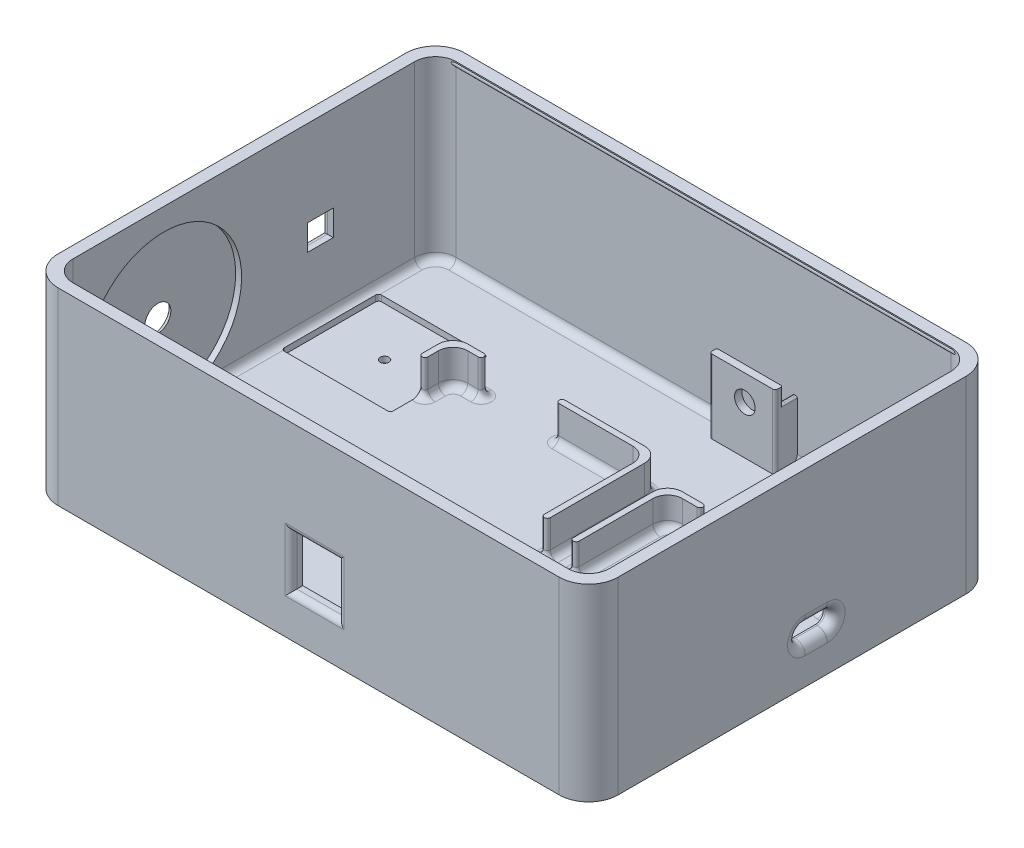
SolidWorks part; units mm, degrees
ref_plane "Front Plane" through (0, 0, 0) normal (0, 0, 1) x (1, 0, 0)
ref_plane "Top Plane" through (0, 0, 0) normal (0, 1, 0) x (1, 0, 0)
ref_plane "Right Plane" through (0, 0, 0) normal (1, 0, 0) x (0, 0, -1)
sketch "Sketch1" plane through (0, 0, 0) normal (0, 1, 0) x (1, 0, 0)
  line L0 (-95, -69) -> (-95, 69)
  line L1 (-91, -65) -> (91, -65)
  line L2 (-91, -65) -> (-91, 65)
  line L3 (-91, 65) -> (91, 65)
  line L4 (91, -65) -> (91, 65)
  line L5 (-91, -65) -> (91, 65) construction
  line L6 (-91, 65) -> (91, -65) construction
  line L7 (-95, 69) -> (95, 69)
  line L8 (95, -69) -> (95, 69)
  line L9 (-95, -69) -> (95, -69)
  point P0 (0, 0)
  dimension "D2" = 130
  dimension "D3" = 182
  dimension "D1" = 4
extrude "Box Sides" add sketch "Sketch1" along normal blind 60
fillet "Fillet1" radius 7 4 edges at (91, 30, 65) (91, 30, -65) (-91, 30, 65) (-91, 30, -65)
fillet "Fillet2" radius 10 4 edges at (95, 30, -69) (95, 30, 69) (-95, 30, 69) (-95, 30, -69)
sketch "Sketch2" plane through (0, 0, 0) normal (0, -1, 0) x (1, 0, 0)
  line L0 (-95, 59) -> (-95, -59)
  line L1 (-85, -69) -> (85, -69)
  line L2 (95, -59) -> (95, 59)
  line L3 (85, 69) -> (-85, 69)
  line L4 (-85, -69) -> (85, -69)
  line L5 (95, -59) -> (95, 59)
  line L6 (85, 69) -> (-85, 69)
  line L7 (-95, 59) -> (-95, -59)
  line L8 (-85, -69) -> (85, -69)
  line L9 (95, -59) -> (95, 59)
  line L10 (85, 69) -> (-85, 69)
  line L11 (-95, 59) -> (-95, -59)
  arc A0 (-85, 69) -> (-95, 59) centre (-85, 59) ccw
  arc A1 (-95, -59) -> (-85, -69) centre (-85, -59) ccw
  arc A2 (85, -69) -> (95, -59) centre (85, -59) ccw
  arc A3 (95, 59) -> (85, 69) centre (85, 59) ccw
  arc A4 (85, -69) -> (95, -59) centre (85, -59) ccw
  arc A5 (95, 59) -> (85, 69) centre (85, 59) ccw
  arc A6 (-85, 69) -> (-95, 59) centre (-85, 59) ccw
  arc A7 (-95, -59) -> (-85, -69) centre (-85, -59) ccw
  arc A8 (85, -69) -> (95, -59) centre (85, -59) ccw
  arc A9 (95, 59) -> (85, 69) centre (85, 59) ccw
  arc A10 (-85, 69) -> (-95, 59) centre (-85, 59) ccw
  arc A11 (-95, -59) -> (-85, -69) centre (-85, -59) ccw
  line M9 (-85, -69) -> (85, -69)
  arc M10 (85, -69) -> (95, -59) centre (85, -59) ccw
  line M11 (95, -59) -> (95, 59)
  arc M12 (95, 59) -> (85, 69) centre (85, 59) ccw
  line M13 (85, 69) -> (-85, 69)
  arc M14 (-85, 69) -> (-95, 59) centre (-85, 59) ccw
  line M15 (-95, 59) -> (-95, -59)
  arc M16 (-95, -59) -> (-85, -69) centre (-85, -59) ccw
  line M17 (-84, 65) -> (84, 65)
  arc M18 (84, 65) -> (91, 58) centre (84, 58) cw
  line M19 (91, 58) -> (91, -58)
  arc M20 (91, -58) -> (84, -65) centre (84, -58) cw
  line M21 (84, -65) -> (-84, -65)
  arc M22 (-84, -65) -> (-91, -58) centre (-84, -58) cw
  line M23 (-91, -58) -> (-91, 58)
  arc M24 (-91, 58) -> (-84, 65) centre (-84, 58) cw
  dimension "D1" = 0
extrude "Bottom" add sketch "Sketch2" along normal blind 4 contours M17 M24 M23 M22 M21 M20 M19 M18 | M16 M9 M10 M11 M12 M13 M14 M15 M24 M17 M18 M19 M20 M21 M22 M23 region at (-90.4106, 0, 64.4106) region at (0, 0, 0)
sketch "Sketch3" plane through (-95, 0, 0) normal (-1, 0, 0) x (0, 0, 1)
  line L1 (-30.35, 22.1) -> (-21.65, 22.1)
  line L2 (-30.35, 22.1) -> (-30.35, 30.8)
  line L3 (-30.35, 30.8) -> (-21.65, 30.8)
  line L4 (-59, 60) -> (-59, -4)
  line L5 (-59, -4) -> (59, -4)
  line L6 (59, -4) -> (59, 60)
  line L7 (59, 60) -> (-59, 60)
  line L8 (-59, 60) -> (-59, -4)
  line L9 (-59, -4) -> (59, -4)
  line L10 (59, -4) -> (59, 60)
  line L11 (59, 60) -> (-59, 60)
  line L12 (-21.65, 22.1) -> (-21.65, 30.8)
  line L13 (-30.35, 22.1) -> (-21.65, 30.8) construction
  line L14 (-30.35, 30.8) -> (-21.65, 22.1) construction
  line L19 (-58, 0) -> (58, 0) construction
  circle A8 centre (27.15, 26.1) radius 4.35
  point P2 (-26, 26.45)
  point P9 (27.15, 26.1)
  point P16 (0, 60)
  dimension "D4" = 8.7
  dimension "D2" = 26
  dimension "D3" = 27.15
  dimension "D5" = 8.7
  dimension "D6" = 26.1
  dimension "D7" = 26.1
  dimension "D1" = 0
extrude "Camera Holes" cut sketch "Sketch3" against normal up to next contours L2 L1 L12 L3 | A8
sketch "Sketch4" plane through (0, 0, 0) normal (0, 1, 0) x (1, 0, 0)
  line L0 (27.8, 25) -> (37.8, 25)
  line L1 (27.8, 25) -> (27.8, -5)
  line L3 (81, 27) -> (91, 27)
  line L4 (-84, -65) -> (84, -65)
  line L5 (91, -58) -> (91, 58)
  line L6 (84, 65) -> (-84, 65)
  line L7 (-91, 58) -> (-91, -58)
  line L8 (-84, -65) -> (84, -65)
  line L9 (91, -58) -> (91, 58)
  line L10 (84, 65) -> (-84, 65)
  line L11 (-91, 58) -> (-91, -58)
  line L12 (27.8, -35) -> (27.8, -65)
  line L13 (25.8, 27) -> (37.8, 27)
  line L14 (25.8, 27) -> (25.8, -5)
  line L15 (81, 25) -> (91, 25)
  line L16 (25.8, -35) -> (25.8, -65)
  line L17 (25.8, -65) -> (27.8, -65)
  line L18 (91, 27) -> (91, 25)
  arc A0 (37.8, 25) -> (37.8, 27) centre (37.8, 26) ccw
  arc A1 (27.8, -5) -> (25.8, -5) centre (26.8, -5) cw
  arc A2 (81, 27) -> (81, 25) centre (81, 26) ccw
  arc A4 (-91, -58) -> (-84, -65) centre (-84, -58) ccw
  arc A5 (84, -65) -> (91, -58) centre (84, -58) ccw
  arc A6 (91, 58) -> (84, 65) centre (84, 58) ccw
  arc A7 (-84, 65) -> (-91, 58) centre (-84, 58) ccw
  arc A8 (-91, -58) -> (-84, -65) centre (-84, -58) ccw
  arc A9 (84, -65) -> (91, -58) centre (84, -58) ccw
  arc A10 (91, 58) -> (84, 65) centre (84, 58) ccw
  arc A11 (-84, 65) -> (-91, 58) centre (-84, 58) ccw
  arc A12 (27.8, -35) -> (25.8, -35) centre (26.8, -35) ccw
  dimension "D8" = 2
  dimension "D2" = 63.2
  dimension "D3" = 10
  dimension "D4" = 10
  dimension "D5" = 90
  dimension "D6" = 30
  dimension "D7" = 30
  dimension "D1" = 0
extrude "Battery Cage" add sketch "Sketch4" along normal blind 10 contours A1 L1 L0 A0 L13 L14 | L3 A2 L15 L9 | L12 A12 L16 L8 | L3 L18 L15 A2 region at (27.4453, 0, -10) region at (85.605, 0, -26) region at (26.8, 0, 49.6065)
sketch "Sketch5" plane through (0, 0, 0) normal (0, 1, 0) x (1, 0, 0)
  line L0 (16, -65) -> (16, -35)
  line L1 (16, 30) -> (16, -5)
  line L2 (-54.4, -30) -> (-54.4, -65)
  line L3 (16, 30) -> (-14, 30)
  line L4 (-41.5, 30) -> (-50, 30)
  line L5 (-50, 30) -> (-50, 21.5)
  line L7 (-60.5, 21.5) -> (-60.5, 38.9191)
  line L8 (-60.5, 38.9191) -> (-41.5, 38.9191)
  line L10 (91, -58) -> (91, 25)
  line L11 (91, 25) -> (81, 25)
  line L12 (81, 27) -> (91, 27)
  line L13 (91, 27) -> (91, 58)
  line L14 (84, 65) -> (-84, 65)
  line L15 (-91, 58) -> (-91, -58)
  line L16 (-84, -65) -> (25.8, -65)
  line L17 (25.8, -65) -> (25.8, -35)
  line L18 (27.8, -35) -> (27.8, -65)
  line L19 (27.8, -65) -> (84, -65)
  line L20 (91, -58) -> (91, 25)
  line L21 (91, 25) -> (81, 25)
  line L22 (81, 27) -> (91, 27)
  line L23 (91, 27) -> (91, 58)
  line L24 (84, 65) -> (-84, 65)
  line L25 (-91, 58) -> (-91, -58)
  line L26 (-84, -65) -> (25.8, -65)
  line L27 (25.8, -65) -> (25.8, -35)
  line L28 (27.8, -35) -> (27.8, -65)
  line L29 (27.8, -65) -> (84, -65)
  line L30 (-41.5, 32) -> (-52, 32)
  line L31 (-52, 32) -> (-52, 21.5)
  line L32 (18, 32) -> (18, -5)
  line L33 (18, 32) -> (-14, 32)
  line L34 (18, -65) -> (18, -35)
  line L35 (-50, -65) -> (-50, -30)
  line L36 (-54.4, -65) -> (-50, -65)
  line L37 (16, -65) -> (18, -65)
  arc A0 (-41.5, 30) -> (-41.5, 32) centre (-41.5, 31) ccw
  arc A1 (-50, 21.5) -> (-52, 21.5) centre (-51, 21.5) cw
  arc A2 (16, -5) -> (18, -5) centre (17, -5) ccw
  arc A3 (-14, 30) -> (-14, 32) centre (-14, 31) cw
  arc A5 (16, -35) -> (18, -35) centre (17, -35) cw
  arc A8 (-50, -30) -> (-54.4, -30) centre (-52.2, -30) ccw
  arc A9 (81, 27) -> (81, 25) centre (81, 26) ccw
  arc A10 (91, 58) -> (84, 65) centre (84, 58) ccw
  arc A11 (-84, 65) -> (-91, 58) centre (-84, 58) ccw
  arc A12 (-91, -58) -> (-84, -65) centre (-84, -58) ccw
  arc A13 (27.8, -35) -> (25.8, -35) centre (26.8, -35) ccw
  arc A14 (-60.5, 21.5) -> (-50, 21.5) centre (-55.25, 21.5) ccw
  arc A15 (84, -65) -> (91, -58) centre (84, -58) ccw
  arc A17 (81, 27) -> (81, 25) centre (81, 26) ccw
  arc A18 (91, 58) -> (84, 65) centre (84, 58) ccw
  arc A19 (-84, 65) -> (-91, 58) centre (-84, 58) ccw
  arc A20 (-91, -58) -> (-84, -65) centre (-84, -58) ccw
  arc A21 (27.8, -35) -> (25.8, -35) centre (26.8, -35) ccw
  arc A23 (84, -65) -> (91, -58) centre (84, -58) ccw
  dimension "D2" = 66
  dimension "D3" = 95
  dimension "D4" = 8.5
  dimension "D5" = 8.5
  dimension "D6" = 30
  dimension "D7" = 35
  dimension "D8" = 2
  dimension "D9" = 73
  dimension "D10" = 4.4
  dimension "D11" = 10.5
  dimension "D1" = 0
extrude "Pi Cage" add sketch "Sketch5" along normal blind 12 contours L1 A2 L32 L33 A3 L3 | A1 L31 L30 A0 L4 L5 | L35 A8 L2 L36 | L0 A5 L34 L37
fillet "Fillet3" radius 5 10 edges at (27.8, 5, -25) (91, 5, -25) (27.8, 5, 65) (25.8, 5, -27) (16, 6, 65) (-50, 6, 65) (18, 6, -32) (-50, 6, -30) (-52, 6, -32) (16, 6, -30)
fillet "Fillet4" radius 2.5 1 edges at (-95, 26.1, 31.5)
sketch "Sketch14" plane through (95, 0, 0) normal (1, 0, 0) x (0, 0, -1)
  line L0 (4.5, 11.2) -> (12, 11.2) construction
  line L1 (4.5, 13.8) -> (12, 13.8)
  line L2 (4.5, 8.6) -> (12, 8.6)
  line L3 (25.5, 60) -> (25.5, -4) construction
  line L4 (-59, 60) -> (-59, -4)
  line L5 (-59, -4) -> (59, -4)
  line L6 (59, -4) -> (59, 60)
  line L7 (59, 60) -> (-59, 60)
  line L8 (-59, 60) -> (-59, -4)
  line L9 (-59, -4) -> (59, -4)
  line L10 (59, -4) -> (59, 60)
  line L11 (59, 60) -> (-59, 60)
  line L12 (-65, 60) -> (-65, 0) construction
  arc A0 (4.5, 13.8) -> (4.5, 8.6) centre (4.5, 11.2) ccw
  arc A1 (12, 8.6) -> (12, 13.8) centre (12, 11.2) ccw
  point P6 (8.25, 11.2)
  dimension "D2" = 90.5
  dimension "D4" = 2.6
  dimension "D3" = 5.2
  dimension "D5" = 7.5
  dimension "D7" = 15.2
  dimension "D8" = 17.25
  dimension "D1" = 0
extrude "Power Button" cut sketch "Sketch14" against normal up to next contours L2 A1 L1 A0 region at (95, 11.2, -8.25)
fillet "Fillet5" radius 3.4 4 edges at (95, 11.2, -1.9) (95, 13.8, -8.25) (95, 11.2, -14.6) (95, 8.6, -8.25)
sketch "Sketch15" plane through (0, 0, 69) normal (0, 0, 1) x (1, 0, 0)
  line L0 (16, 0) -> (16, 12) construction
  line L1 (-6, 27.5) -> (10, 27.5)
  line L2 (-6, 27.5) -> (-6, 10)
  line L3 (-6, 10) -> (10, 10)
  line L4 (-85, 60) -> (-85, -4)
  line L5 (-85, -4) -> (85, -4)
  line L6 (85, -4) -> (85, 60)
  line L7 (85, 60) -> (-85, 60)
  line L8 (-85, 60) -> (-85, -4)
  line L9 (-85, -4) -> (85, -4)
  line L10 (85, -4) -> (85, 60)
  line L11 (85, 60) -> (-85, 60)
  line L12 (10, 27.5) -> (10, 10)
  line L13 (-6, 27.5) -> (10, 10) construction
  line L14 (-6, 10) -> (10, 27.5) construction
  point P2 (2, 18.75)
  dimension "D2" = 16
  dimension "D3" = 17.5
  dimension "D4" = 6
  dimension "D5" = 14
  dimension "D1" = 0
extrude "USBs" cut sketch "Sketch15" against normal up to next contours L2 L1 L12 L3
fillet "Fillet6" radius 2 4 edges at (2, 27.5, 69) (10, 18.75, 69) (-6, 18.75, 69) (2, 10, 69)
sketch "Sketch17" plane through (0, 0, 0) normal (0, 1, 0) x (1, 0, 0)
  line L0 (11, 60) -> (30.3, 60)
  line L1 (85, 69) -> (-85, 69) construction
  line L2 (11, 57.5) -> (30.3, 57.5)
  line L3 (20.65, 57.5) -> (20.65, 27.5) construction
  line L4 (11, 60) -> (11, 65)
  line L6 (30.3, 60) -> (30.3, 65)
  line L7 (84, 65) -> (-84, 65) construction
  line L8 (11, 65) -> (9.5, 65)
  line L9 (9.5, 65) -> (9.5, 58.4)
  line L10 (10.4, 57.5) -> (11, 57.5)
  line L11 (30.3, 57.5) -> (30.9, 57.5)
  line L12 (31.8, 58.4) -> (31.8, 65)
  line L13 (31.8, 65) -> (30.3, 65)
  line L16 (-45, -65) -> (11, -65)
  line L20 (-45, -65) -> (11, -65)
  line L24 (16, -60) -> (16, -35)
  line L28 (16, -60) -> (16, -35)
  line L66 (18, -35) -> (18, -65)
  line L68 (18, -35) -> (18, -65)
  line L84 (18, -65) -> (25.8, -65)
  line L92 (18, -65) -> (25.8, -65)
  line L100 (25.8, -65) -> (25.8, -35)
  line L104 (25.8, -65) -> (25.8, -35)
  line L108 (27.8, -35) -> (27.8, -60)
  line L111 (27.8, -35) -> (27.8, -60)
  line L113 (32.8, -65) -> (84, -65)
  line L115 (32.8, -65) -> (84, -65)
  line L117 (91, -58) -> (91, 20)
  line L119 (91, -58) -> (91, 20)
  line L121 (86, 25) -> (81, 25)
  line L122 (86, 25) -> (81, 25)
  line L123 (81, 27) -> (91, 27)
  line L124 (81, 27) -> (91, 27)
  line L125 (91, 27) -> (91, 58)
  line L126 (91, 27) -> (91, 58)
  line L127 (84, 65) -> (-84, 65)
  line L128 (84, 65) -> (-84, 65)
  line L129 (-91, 58) -> (-91, -58)
  line L130 (-91, 58) -> (-91, -58)
  line L131 (-84, -65) -> (-54.4, -65)
  line L132 (-84, -65) -> (-54.4, -65)
  line L133 (-50, -30) -> (-50, -60)
  line L134 (-50, -30) -> (-50, -60)
  line L135 (-54.4, -65) -> (-54.4, -30)
  line L136 (-54.4, -65) -> (-54.4, -30)
  arc A2 (9.5, 58.4) -> (10.4, 57.5) centre (10.4, 58.4) ccw
  arc A3 (31.8, 58.4) -> (30.9, 57.5) centre (30.9, 58.4) cw
  arc A8 (11, -65) -> (16, -60) centre (11, -60) ccw
  arc A12 (11, -65) -> (16, -60) centre (11, -60) ccw
  arc A28 (18, -35) -> (16, -35) centre (17, -35) ccw
  arc A40 (18, -35) -> (16, -35) centre (17, -35) ccw
  arc A52 (27.8, -35) -> (25.8, -35) centre (26.8, -35) ccw
  arc A54 (27.8, -35) -> (25.8, -35) centre (26.8, -35) ccw
  arc A61 (27.8, -60) -> (32.8, -65) centre (32.8, -60) ccw
  arc A65 (27.8, -60) -> (32.8, -65) centre (32.8, -60) ccw
  arc A69 (84, -65) -> (91, -58) centre (84, -58) ccw
  arc A71 (84, -65) -> (91, -58) centre (84, -58) ccw
  arc A73 (91, 20) -> (86, 25) centre (86, 20) ccw
  arc A75 (91, 20) -> (86, 25) centre (86, 20) ccw
  arc A77 (81, 27) -> (81, 25) centre (81, 26) ccw
  arc A78 (81, 27) -> (81, 25) centre (81, 26) ccw
  arc A79 (91, 58) -> (84, 65) centre (84, 58) ccw
  arc A80 (91, 58) -> (84, 65) centre (84, 58) ccw
  arc A81 (-84, 65) -> (-91, 58) centre (-84, 58) ccw
  arc A82 (-84, 65) -> (-91, 58) centre (-84, 58) ccw
  arc A83 (-91, -58) -> (-84, -65) centre (-84, -58) ccw
  arc A84 (-91, -58) -> (-84, -65) centre (-84, -58) ccw
  arc A85 (-50, -60) -> (-45, -65) centre (-45, -60) ccw
  arc A86 (-50, -60) -> (-45, -65) centre (-45, -60) ccw
  arc A87 (-50, -30) -> (-54.4, -30) centre (-52.2, -30) ccw
  arc A88 (-50, -30) -> (-54.4, -30) centre (-52.2, -30) ccw
  dimension "D7" = 0.9
  dimension "D8" = 0.9
  dimension "D9" = 22.3
  dimension "D2" = 9
  dimension "D4" = 30
  dimension "D5" = 1.5
  dimension "D6" = 1.5
  dimension "D10" = 81.5
  dimension "D1" = 0
  dimension "D3" = 2.5
sketch "Sketch16" plane through (0, 0, -69) normal (0, 0, -1) x (-1, 0, 0)
  line L4 (85, 60) -> (-85, 60)
  line L5 (-85, 60) -> (-85, -4)
  line L6 (-85, -4) -> (85, -4)
  line L7 (85, -4) -> (85, 60)
  line L8 (85, 60) -> (-85, 60)
  line L9 (-85, 60) -> (-85, -4)
  line L10 (-85, -4) -> (85, -4)
  line L11 (85, -4) -> (85, 60)
  circle A0 centre (-21.5, 16.4) radius 3.5
  dimension "D2" = 7
  dimension "D3" = 63.5
  dimension "D4" = 20.4
  dimension "D1" = 0
fillet "Fillet9" radius 2 4 edges at (-95, 26.45, -30.35) (-95, 22.1, -26) (-95, 26.45, -21.65) (-95, 30.8, -26)
sketch "Sketch19" plane through (0, 0, 0) normal (0, 1, 0) x (1, 0, 0)
  line L0 (-80, -46.125) -> (-54.4, -46.125) construction
  line L2 (-89, 41.25) -> (-89, 10.75)
  line L3 (-89, 10.75) -> (-52, 10.75)
  line L4 (-52, 41.25) -> (-52, 10.75)
  line L5 (-89, 41.25) -> (-52, 10.75) construction
  line L6 (-89, 10.75) -> (-52, 41.25) construction
  line L7 (-80, -8.175) -> (-54.4, -8.175)
  line L8 (-80, -8.175) -> (-80, -48.625)
  line L9 (-80, -48.625) -> (-54.4, -48.625)
  line L10 (-54.4, -8.175) -> (-54.4, -48.625)
  line L11 (-54.4, -8.175) -> (-80, -46.125) construction
  line L12 (-80, -8.175) -> (-54.4, -46.125) construction
  line L13 (-89, 43.75) -> (-52, 43.75) construction
  line L15 (-35.2, 0) -> (35.2, 0) construction
  line L16 (-89, 43.75) -> (-89, 41.25)
  line L17 (-89, 43.75) -> (-52, 43.75)
  line L18 (-52, 43.75) -> (-52, 41.25)
  line L19 (-52, 27) -> (-52, 21.5) construction
  line L21 (-45, -65) -> (11, -65)
  line L67 (-45, -65) -> (11, -65)
  line L94 (16, -60) -> (16, -35)
  line L102 (16, -60) -> (16, -35)
  line L106 (18, -35) -> (18, -65)
  line L110 (18, -35) -> (18, -65)
  line L114 (18, -65) -> (25.8, -65)
  line L124 (18, -65) -> (25.8, -65)
  line L132 (25.8, -65) -> (25.8, -35)
  line L137 (25.8, -65) -> (25.8, -35)
  line L141 (27.8, -35) -> (27.8, -60)
  line L144 (27.8, -35) -> (27.8, -60)
  line L146 (32.8, -65) -> (84, -65)
  line L148 (32.8, -65) -> (84, -65)
  line L150 (91, -58) -> (91, 20)
  line L152 (91, -58) -> (91, 20)
  line L154 (86, 25) -> (81, 25)
  line L155 (86, 25) -> (81, 25)
  line L156 (81, 27) -> (91, 27)
  line L157 (81, 27) -> (91, 27)
  line L158 (91, 27) -> (91, 58)
  line L159 (91, 27) -> (91, 58)
  line L160 (84, 65) -> (-84, 65)
  line L161 (84, 65) -> (-84, 65)
  line L162 (-91, 58) -> (-91, -58)
  line L163 (-91, 58) -> (-91, -58)
  line L164 (-84, -65) -> (-54.4, -65)
  line L165 (-84, -65) -> (-54.4, -65)
  line L166 (-50, -30) -> (-50, -60)
  line L167 (-50, -30) -> (-50, -60)
  line L168 (-54.4, -65) -> (-54.4, -30)
  line L169 (-54.4, -65) -> (-54.4, -30)
  arc A8 (11, -65) -> (16, -60) centre (11, -60) ccw
  arc A46 (11, -65) -> (16, -60) centre (11, -60) ccw
  arc A48 (18, -35) -> (16, -35) centre (17, -35) ccw
  arc A58 (18, -35) -> (16, -35) centre (17, -35) ccw
  arc A70 (27.8, -35) -> (25.8, -35) centre (26.8, -35) ccw
  arc A72 (27.8, -35) -> (25.8, -35) centre (26.8, -35) ccw
  arc A79 (27.8, -60) -> (32.8, -65) centre (32.8, -60) ccw
  arc A83 (27.8, -60) -> (32.8, -65) centre (32.8, -60) ccw
  arc A87 (84, -65) -> (91, -58) centre (84, -58) ccw
  arc A89 (84, -65) -> (91, -58) centre (84, -58) ccw
  arc A91 (91, 20) -> (86, 25) centre (86, 20) ccw
  arc A93 (91, 20) -> (86, 25) centre (86, 20) ccw
  arc A95 (81, 27) -> (81, 25) centre (81, 26) ccw
  arc A96 (81, 27) -> (81, 25) centre (81, 26) ccw
  arc A97 (91, 58) -> (84, 65) centre (84, 58) ccw
  arc A98 (91, 58) -> (84, 65) centre (84, 58) ccw
  arc A99 (-84, 65) -> (-91, 58) centre (-84, 58) ccw
  arc A100 (-84, 65) -> (-91, 58) centre (-84, 58) ccw
  arc A101 (-91, -58) -> (-84, -65) centre (-84, -58) ccw
  arc A102 (-91, -58) -> (-84, -65) centre (-84, -58) ccw
  arc A103 (-50, -60) -> (-45, -65) centre (-45, -60) ccw
  arc A104 (-50, -60) -> (-45, -65) centre (-45, -60) ccw
  arc A105 (-50, -30) -> (-54.4, -30) centre (-52.2, -30) ccw
  arc A106 (-50, -30) -> (-54.4, -30) centre (-52.2, -30) ccw
  point P0 (-70.5, 26)
  point P28 (-67.2, -27.15)
  dimension "D2" = 37
  dimension "D3" = 25.6
  dimension "D4" = 2.5
  dimension "D5" = 30.5
  dimension "D7" = 26
  dimension "D8" = 2.5
  dimension "D10" = 30.85
  dimension "D11" = 37.95
  dimension "D1" = 0
extrude "Cam Mounts" cut sketch "Sketch19" against normal blind 2 contours L2 L3 L4 L18 L17 L16 | L8 L7 L10 L9
fillet "Fillet15" radius 2.5 41 edges at (-43.25, 0, -30) (-40.5, 0, -31) (-44.25, 0, -32) (-50.5355, 0, -30.5355) (-51, 0, -20.5) (-50, 0, -23.25) (16.5355, 0, -30.5355) (-0.5, 0, -32) (-15, 0, -31) (-1.5, 0, -30) (14.5355, 0, -28.5355) (16, 0, -10) (17, 0, 6) (29.2645, 0, -23.5355) (35.3, 0, -25) (38.8, 0, -26) (34.3, 0, -27) (27.2645, 0, -25.5355) (25.8, 0, -8.5) (26.8, 0, 6) (25.8, 0, 50) (26.8, 0, 34) (27.8, 0, 47.5) (29.2645, 0, 63.5355) (86, 0, -27) (80, 0, -26) (83.5, 0, -25) (89.5355, 0, -23.5355) (91, 0, 19) (88.9497, 0, 62.9497) (91, 0, -42.5) (88.9497, 0, -62.9497) (-69.2, 0, 65) (-88.9497, 0, 62.9497) (-91, 0, 0) (-88.9497, 0, -62.9497) (-48.5355, 0, -28.5355) (18, 0, -11) (27.8, 0, -7.5) (58.4, 0, 65) (0, 0, -65)
extrude "Button Mount" add sketch "Sketch17" along normal blind 25 contours A3 L12 L6 L0 L4 L9 A2 L10 L2 L11 | L8 L9 L4 | L12 L13 L6 region at (20.65, 0, -59.5542)
extrude "Button Hole" cut sketch "Sketch16" against normal blind 20 contours A0
fillet "Fillet11" radius 3 1 edges at (18, 16.4, -69)
fillet "Fillet12" radius 1 7 edges at (-52, -1, -10.75) (-89, -0.9747, -10.75) (-54.4, -1, 48.625) (-80, -1, 8.175) (-80, -1, 48.625) (-52, -1, -43.75) (-89, -0.9747, -43.75)
sketch "Sketch20" plane through (0, 25, 0) normal (0, 1, 0) x (1, 0, 0)
  line L0 (11, 60) -> (9.5, 60)
  line L1 (9.5, 60) -> (31.8, 60)
  line L8 (31.8, 58.4) -> (31.8, 65)
  line L9 (31.8, 65) -> (30.3, 65)
  line L10 (30.3, 65) -> (30.3, 60)
  line L11 (30.3, 60) -> (11, 60)
  line L12 (11, 60) -> (11, 65)
  line L13 (11, 65) -> (9.5, 65)
  line L14 (9.5, 65) -> (9.5, 58.4)
  line L15 (10.4, 57.5) -> (30.9, 57.5)
  line L16 (31.8, 58.4) -> (31.8, 65)
  line L17 (31.8, 65) -> (30.3, 65)
  line L18 (30.3, 65) -> (30.3, 60)
  line L19 (30.3, 60) -> (11, 60)
  line L20 (11, 60) -> (11, 65)
  line L21 (11, 65) -> (9.5, 65)
  line L22 (9.5, 65) -> (9.5, 58.4)
  line L23 (10.4, 57.5) -> (30.9, 57.5)
  arc A2 (30.9, 57.5) -> (31.8, 58.4) centre (30.9, 58.4) ccw
  arc A3 (9.5, 58.4) -> (10.4, 57.5) centre (10.4, 58.4) ccw
  arc A4 (30.9, 57.5) -> (31.8, 58.4) centre (30.9, 58.4) ccw
  arc A5 (9.5, 58.4) -> (10.4, 57.5) centre (10.4, 58.4) ccw
  line M12 (31.8, 58.4) -> (31.8, 65)
  line M13 (31.8, 65) -> (30.3, 65)
  line M14 (30.3, 65) -> (30.3, 60)
  line M16 (11, 60) -> (11, 65)
  line M17 (11, 65) -> (9.5, 65)
  line M18 (9.5, 65) -> (9.5, 58.4)
  dimension "D1" = 0
extrude "Button Supports" cut sketch "Sketch20" against normal blind 5.5 contours L0 M16 M17 M18 | L1 M14 M12 M13 region at (10.25, 25, -62.5) region at (31.05, 25, -62.5)
fillet "Fillet13" radius 0.5 6 edges at (9.5, 22.25, -60) (31.8, 22.25, -60) (9.5, 19.5, -62.5) (11, 19.5, -62.5) (30.3, 19.5, -62.5) (31.8, 19.5, -62.5)
sketch "Sketch21" plane through (0, 0, 0) normal (1, 0, 0) x (0, 0, -1)
  line L0 (65, 59.58) -> (65, 58.42)
  line L1 (65, 60) -> (65, 2.5) construction
  line L3 (69, 60) -> (59, 60) construction
  line L4 (-65, 59.58) -> (-65, 58.42)
  line L5 (-59, 60) -> (-69, 60) construction
  line L8 (-65, 2.5) -> (-65, 60) construction
  arc A0 (65, 59.58) -> (65, 58.42) centre (65.8146, 59) ccw
  arc A1 (-65, 59.58) -> (-65, 58.42) centre (-65.8146, 59) cw
  dimension "D3" = 1
  dimension "D6" = 1
  dimension "D1" = 1.16
  dimension "D2" = 0.42
  dimension "D4" = 1.16
  dimension "D5" = 0.42
extrude "Lid Ridge" add sketch "Sketch21" along normal up to surface and the other way up to surface up to face at (91, 11.2, -8.25) other way up to face at (-91, 26.1, 22.8)
sketch "Sketch22" plane through (-91, 0, 0) normal (1, 0, 0) x (0, 0, -1)
  line L4 (-58, 60) -> (-58, 2.5)
  line L5 (-58, 2.5) -> (58, 2.5)
  line L6 (58, 2.5) -> (58, 60)
  line L7 (58, 60) -> (-58, 60)
  line L8 (-58, 60) -> (-58, 2.5)
  line L10 (58, 2.5) -> (58, 60)
  line L11 (58, 60) -> (-58, 60)
  line L15 (-58, 2.5) -> (58, 2.5)
  circle A0 centre (-27.15, 26.1) radius 26.4
  circle M5 centre (-27.15, 26.1) radius 4.35
  dimension "D2" = 52.8
  dimension "D1" = 0
extrude "Holder Insert" cut sketch "Sketch22" against normal blind 2.01 and the other way blind 14 contours L11 A0 M5 | L11 A0 | A0 region at (-91, 47.946, 40.6351) region at (-91, 1.3747, 27.15)
sketch "Sketch24" plane through (0, -2, 0) normal (0, 1, 0) x (1, 0, 0)
  line L0 (-89, 42.75) -> (-89, 11.75) construction
  line L1 (-88, 10.75) -> (-53, 10.75) construction
  line L2 (-80, -9.175) -> (-80, -47.625) construction
  line L3 (-79, -48.625) -> (-55.4, -48.625) construction
  circle A0 centre (-70.5, 27.25) radius 1.5
  circle A1 centre (-67.2, -28.4) radius 1.5
  point P4 (-70.5, 10.75)
  point P7 (-89, 27.25)
  point P13 (-80, -28.4)
  point P16 (-67.2, -48.625)
  dimension "D1" = 3
extrude "Cut-Extrude1" cut sketch "Sketch24" against normal through all
equation "\"A\"= ( \"B\" - 20 ) / 4"
equation "\"B\"=108.204"
